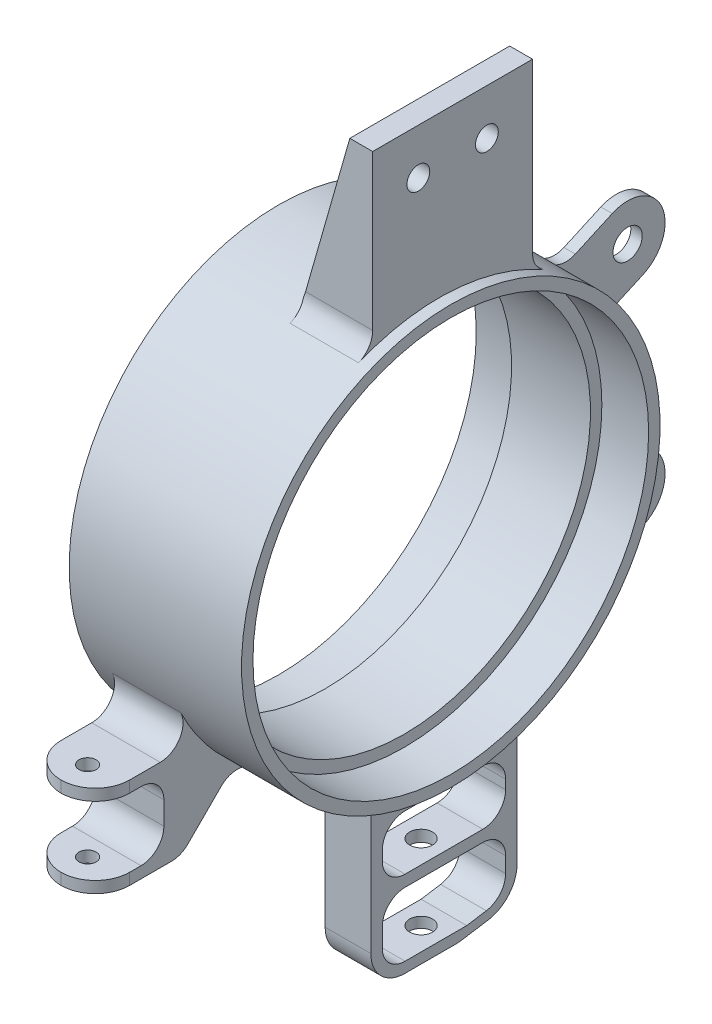
SolidWorks part; units mm, degrees
ref_plane "Front Plane" through (0, 0, 0) normal (0, 0, 1) x (1, 0, 0)
ref_plane "Top Plane" through (0, 0, 0) normal (0, 1, 0) x (1, 0, 0)
ref_plane "Right Plane" through (0, 0, 0) normal (1, 0, 0) x (0, 0, -1)
sketch "Sketch1" plane through (0, 0, 0) normal (0, 0, 1) x (1, 0, 0)
  line L0 (47.925, 0) -> (0, 0) construction
  line L1 (47.925, 55) -> (34.925, 55)
  line L2 (34.925, 55) -> (34.925, 51.825)
  line L3 (34.925, 51.825) -> (13, 51.825)
  line L4 (13, 51.825) -> (13, 55)
  line L5 (13, 55) -> (0, 55)
  line L6 (47.925, 55) -> (47.925, 58.175)
  line L7 (47.925, 58.175) -> (0, 58.175)
  line L8 (0, 58.175) -> (0, 55)
  line L9 (41.425, 55) -> (58.951, 55) construction
  point P11 (6.5, 55)
  point P12 (41.425, 55)
  dimension "D2" = 3.175
  dimension "D3" = 13
  dimension "D4" = 34.925
  dimension "D5" = 3.175
  dimension "D6" = 17.526
  dimension "D7" = 55
revolve "Revolve1" add sketch "Sketch1" angle 360 about L0 reverse direction yes
ref_plane "upper a-arm plane" through (0, 58.175, 0) normal (0, 1, 0) x (1, 0, 0)
ref_plane "rear tierod plane" through (0, 0, 76.2) normal (0, 0, 1) x (1, 0, 0)
sketch "Sketch2" plane through (0, 0, 76.2) normal (0, 0, 1) x (1, 0, 0)
  line L1 (6.254, -34.29) -> (25.304, -34.29)
  line L2 (6.254, -34.29) -> (6.254, -37.465)
  line L3 (6.254, -37.465) -> (25.304, -37.465)
  line L4 (25.304, -34.29) -> (25.304, -37.465)
  point P6 (15.779, -46.99)
  point P10 (15.779, -37.465)
  dimension "D1" = 9.525
  dimension "D2" = 19.05
  dimension "D3" = 3.175
extrude "Boss-Extrude1" add sketch "Sketch2" against normal up to surface (29.205 mm away) up to face at (0, -58.175, 0)
sketch "Sketch4" plane through (0, 58.175, 0) normal (0, 1, 0) x (1, 0, 0)
  line L0 (38.3366, 19.6167) -> (38.3366, -12.1333)
  line L1 (38.3366, -12.1333) -> (25.6366, -12.1333)
  line L2 (25.6366, -12.1333) -> (25.6366, -18.4833)
  line L3 (25.6366, -18.4833) -> (44.6866, -18.4833)
  line L4 (44.6866, -18.4833) -> (44.6866, 25.9667)
  line L5 (44.6866, 25.9667) -> (25.6366, 25.9667)
  line L6 (25.6366, 25.9667) -> (25.6366, 19.6167)
  line L7 (25.6366, 19.6167) -> (38.3366, 19.6167)
  point P2 (19.2866, 3.7417)
  point P11 (38.3366, 3.7417)
  dimension "D1" = 31.75
  dimension "D2" = 6.35
  dimension "D3" = 6.35
  dimension "D4" = 19.05
  dimension "D5" = 12.7
extrude "Boss-Extrude2" add sketch "Sketch4" along normal blind 44.45 and the other way up to surface other way up to face at (15.779, -35.8883, 45.7638)
sketch "Sketch5" plane through (0, 0, 18.4833) normal (0, 0, 1) x (1, 0, 0)
  line L0 (38.3366, 102.625) -> (25.6366, 58.175)
  line L1 (47.925, 58.175) -> (0, 58.175) construction
  line L2 (25.6366, 102.625) -> (25.6366, 55.1607) construction
  line L3 (25.6366, 58.175) -> (25.6366, 102.625)
  line L4 (25.6366, 102.625) -> (38.3366, 102.625)
extrude "Cut-Extrude1" cut sketch "Sketch5" against normal through all both and the other way through all
ref_plane "Plane3" through (0, -58.175, 0) normal (0, -1, 0) x (-1, 0, 0)
sketch "Sketch7" plane through (0, -58.175, 0) normal (0, -1, 0) x (-1, 0, 0)
  line L9 (-32.289, 34.0454) -> (-19.589, 34.0454)
  line L10 (-32.289, 34.0454) -> (-32.289, -6.5946)
  line L11 (-32.289, -6.5946) -> (-19.589, -6.5946)
  line L12 (-19.589, 34.0454) -> (-19.589, -6.5946)
  line L13 (-32.289, 34.0454) -> (-19.589, -6.5946) construction
  line L14 (-32.289, -6.5946) -> (-19.589, 34.0454) construction
  point P0 (-25.939, 13.7254)
  dimension "D1" = 12.7
  dimension "D2" = 40.64
extrude "Boss-Extrude3" add sketch "Sketch7" against normal up to surface and the other way blind 53.975
sketch "Sketch8" plane through (32.289, 0, 0) normal (1, 0, 0) x (0, 0, -1)
  line L0 (34.0454, -112.15) -> (34.0454, -47.1725) construction
  line L13 (13.7254, -101.6) -> (13.7254, -109.22) construction
  line L14 (-3.4196, -109.22) -> (20.0754, -109.22)
  line L15 (-3.4196, -91.44) -> (30.8704, -91.44)
  line L16 (-3.4196, -109.22) -> (-3.4196, -91.44)
  line L17 (13.7254, -109.22) -> (13.7254, -114.7521) construction
  line L18 (-6.5946, -112.15) -> (-6.5946, -57.8) construction
  line L22 (1.0254, -106.68) -> (26.4254, -106.68) construction
  line L24 (30.8704, -91.44) -> (30.8704, -107.5246)
  line L25 (20.0754, -109.22) -> (30.8704, -107.5246)
  line L28 (17.7905, -112.15) -> (34.0454, -109.597)
  line L29 (-3.4196, -73.025) -> (30.8704, -73.025)
  line L30 (-3.4196, -73.025) -> (-3.4196, -88.265)
  line L31 (-3.4196, -88.265) -> (30.8704, -88.265)
  line L32 (30.8704, -73.025) -> (30.8704, -88.265)
  line L33 (-3.4196, -73.025) -> (30.8704, -88.265) construction
  line L34 (-3.4196, -88.265) -> (30.8704, -73.025) construction
  line L35 (34.0454, -112.15) -> (-6.5946, -112.15) construction
  line L36 (34.0454, -109.597) -> (34.0454, -112.15)
  line L37 (34.0454, -112.15) -> (17.7905, -112.15)
  circle A1 centre (0, 0) radius 115.57 construction
  point P7 (13.7254, -109.22)
  point P15 (13.7254, -91.44)
  point P20 (13.7254, -106.68)
  point P22 (0, 0)
  point P24 (13.7254, -80.645)
  point P27 (0, 0)
  dimension "D1" = 6.35
  dimension "D2" = 7.62
  dimension "D3" = 10.16
  dimension "D4" = 2.54
  dimension "D5" = 25.4
  dimension "D6" = 5.08
  dimension "D7" = 3.175
  dimension "D8" = 7.62
  dimension "D9" = 1.524
  dimension "D11" = 3.175
  dimension "D12" = 15.24
extrude "Cut-Extrude4" cut sketch "Sketch8" against normal through all
sketch "Sketch9" plane through (25.304, 0, 0) normal (1, 0, 0) x (0, 0, -1)
  line L0 (-44.5051, -37.465) -> (-57.15, -37.465)
  line L1 (-44.5051, -37.465) -> (-76.2, -37.465) construction
  line L2 (-57.15, -37.465) -> (-57.15, -56.515)
  line L3 (-57.15, -56.515) -> (-76.2, -56.515)
  line L5 (-76.2, -59.69) -> (-52.3617, -59.69)
  line L6 (-52.3617, -59.69) -> (-37.3083, -44.6366)
  line L9 (-76.2, -59.69) -> (-76.2, -56.515)
  line L10 (-76.2, -37.465) -> (-76.2, -34.29) construction
  circle A0 centre (0, 0) radius 58.175 construction
  arc A1 (-44.5051, -37.465) -> (-37.3083, -44.6366) centre (0, 0) ccw
  dimension "D1" = 19.05
  dimension "D2" = 3.175
  dimension "D3" = 19.05
  dimension "D4" = 10.16
  dimension "D5" = 45
sketch "Sketch10" plane through (30.0204, 0, 0) normal (-1, 0, 0) x (0, 0, 1)
  line L0 (-56.4595, -14.0233) -> (-71.344, -20.7317)
  line L1 (-62.786, -39.7203) -> (-47.9014, -33.0119)
  line L2 (-67.065, -30.226) -> (0, 0) construction
  line L3 (0, 0) -> (-67.065, 30.226) construction
  line L4 (-47.9014, 33.0119) -> (-62.786, 39.7203)
  line L5 (-71.344, 20.7317) -> (-56.4595, 14.0233)
  circle A0 centre (-67.065, -30.226) radius 4.064 construction
  circle A1 centre (-67.065, -30.226) radius 4.064
  circle A2 centre (-67.065, 30.226) radius 4.064 construction
  circle A3 centre (-67.065, 30.226) radius 4.064
  circle A4 centre (0, 0) radius 58.175 construction
  arc A5 (-47.9014, 33.0119) -> (-56.4595, 14.0233) centre (0, 0) ccw
  arc A6 (-71.344, -20.7317) -> (-62.786, -39.7203) centre (-67.065, -30.226) ccw
  arc A7 (-62.786, 39.7203) -> (-71.344, 20.7317) centre (-67.065, 30.226) ccw
  arc A8 (-56.4595, -14.0233) -> (-47.9014, -33.0119) centre (0, 0) ccw
  dimension "D1" = 6.35
  dimension "D2" = 6.35
extrude "Boss-Extrude5" add sketch "Sketch10" along normal blind 3.175
extrude "Boss-Extrude6" add sketch "Sketch9" against normal up to surface (19.05 mm away) up to face at (6.254, -35.8829, 60.9819)
sketch "Sketch6" plane through (0, -34.29, 0) normal (0, 1, 0) x (1, 0, 0)
  circle A0 centre (15.779, -68.8246) radius 2.3813
  dimension "D1" = 4.7625
extrude "Cut-Extrude2" cut sketch "Sketch6" against normal through all both and the other way through all
sketch "Sketch12" plane through (44.6866, 0, 0) normal (1, 0, 0) x (0, 0, -1)
  line L0 (13.2667, 89.925) -> (-5.7833, 89.925) construction
  line L1 (-18.4833, 102.625) -> (25.9667, 102.625) construction
  circle A0 centre (-5.7833, 89.925) radius 3.175
  circle A1 centre (13.2667, 89.925) radius 3.175
  point P6 (3.7417, 102.625)
  point P7 (3.7417, 89.925)
  dimension "D1" = 6.35
  dimension "D2" = 19.05
  dimension "D3" = 12.7
extrude "Cut-Extrude5" cut sketch "Sketch12" against normal through all
fillet "0.25 Fillet5" radius 6.35 21 edges at (25.939, -107.5246, -30.8704) (25.939, -73.025, 3.4196) (25.939, -73.025, -30.8704) (25.939, -88.265, -30.8704) (25.939, -91.44, -30.8704) (25.939, -91.44, 3.4196) (25.939, -88.265, 3.4196) (25.939, -109.22, 3.4196) (35.1616, 55.1607, 18.4833) (35.1616, 52.0583, -25.9667) (28.4329, 14.0233, -56.4595) (28.4329, 33.0119, -47.9014) (28.4329, -14.0233, -56.4595) (28.4329, -33.0119, -47.9014) (15.779, -34.29, 46.995) (15.779, -44.6366, 37.3083) (15.779, -56.515, 57.15) (15.779, -37.465, 57.15) (15.779, -59.69, 52.3617) (31.9866, 56.8956, 12.1333) (31.9866, 54.7678, -19.6167)
sketch "Sketch13" plane through (0, -88.265, 0) normal (0, 1, 0) x (1, 0, 0)
  line L0 (32.289, -3.4196) -> (32.289, 30.8704) construction
  line L1 (32.289, 24.5204) -> (19.589, 24.5204) construction
  circle A0 centre (25.939, 13.7254) radius 3.175
  point P5 (32.289, 13.7254)
  point P8 (25.939, 24.5204)
  dimension "D1" = 6.35
extrude "Cut-Extrude6" cut sketch "Sketch13" against normal through all
fillet "0.375 Fillet6" radius 9.525 9 edges at (25.939, -47.1725, -34.0454) (25.939, -57.8, 6.5946) (25.939, -109.597, -34.0454) (25.939, -112.15, -17.7905) (25.939, -112.15, 6.5946) (25.304, -35.8775, 76.2) (6.254, -35.8775, 76.2) (25.304, -58.1025, 76.2) (6.254, -58.1025, 76.2)
